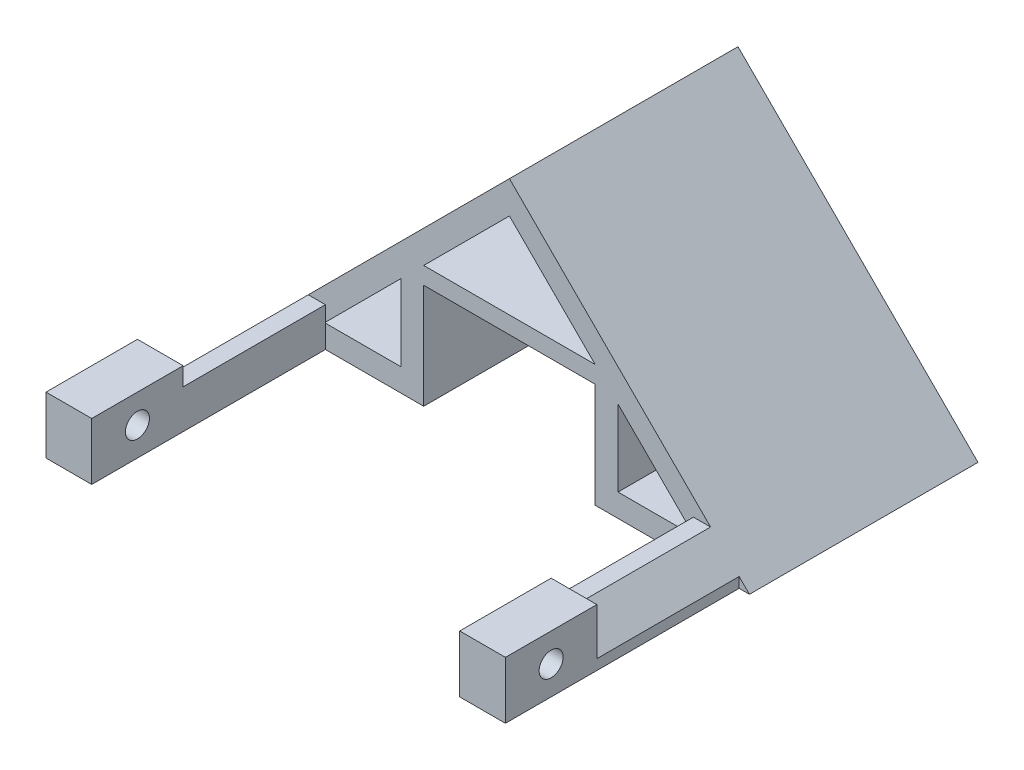
SolidWorks part; units mm, degrees
ref_plane "Front Plane" through (0, 0, 0) normal (0, 0, 1) x (1, 0, 0)
ref_plane "Top Plane" through (0, 0, 0) normal (0, 1, 0) x (1, 0, 0)
ref_plane "Right Plane" through (0, 0, 0) normal (1, 0, 0) x (0, 0, -1)
sketch "Sketch1" plane through (0, 0, 0) normal (0, 0, 1) x (1, 0, 0)
  line L1 (0, 0) -> (-42, -42)
  line L2 (0, -1000.3549) -> (0, 48999.6451) construction
  line L3 (-32.3431, -38) -> (-19, -24.6569)
  line L4 (32.3431, -38) -> (19, -24.6569)
  line L5 (0, 0) -> (42, -42)
  line L7 (-42, -42) -> (-15, -42)
  line L8 (-32.3431, -38) -> (-19, -38)
  line L9 (-34, -34) -> (34, -34) construction
  line L10 (-15, -42) -> (-15, -23.6569)
  line L11 (15, -42) -> (15, -23.6569)
  line L12 (15, -42) -> (42, -42)
  line L13 (19, -38) -> (32.3431, -38)
  line L14 (-19, -38) -> (-19, -24.6569)
  line L15 (19, -38) -> (19, -24.6569)
  line L16 (-15, -20.6569) -> (0, -5.6569)
  line L17 (15, -20.6569) -> (0, -5.6569)
  line L18 (15, -20.6569) -> (-15, -20.6569)
  line L19 (15, -23.6569) -> (-15, -23.6569)
  point P21 (0, -23.6569)
  dimension "D1" = 90
  dimension "D2" = 4
  dimension "D3" = 4
  dimension "D4" = 68
  dimension "D5" = 8
  dimension "D6" = 30
  dimension "D7" = 4
  dimension "D8" = 3
extrude "Boss-Extrude1" add sketch "Sketch1" along normal mid plane 40
sketch "Sketch2" plane through (0, 0, 0) normal (1, 0, 0) x (0, 0, -1)
  line L0 (0, -1034.3624) -> (0, 48965.6376) construction
  line L1 (-20, -42) -> (20, -42) construction
  line L2 (-3.5, -42) -> (-3.5, -65.5)
  line L3 (-3.5, -65.5) -> (-9, -65.5)
  line L4 (-9, -65.5) -> (-9, -69)
  line L5 (-9, -69) -> (9, -69)
  line L6 (9, -65.5) -> (9, -69)
  line L7 (3.5, -65.5) -> (9, -65.5)
  line L8 (3.5, -42) -> (3.5, -65.5)
  line L9 (3.5, -42) -> (-3.5, -42)
  point P5 (0, -42)
  dimension "D1" = 7
  dimension "D2" = 3.5
  dimension "D3" = 27
  dimension "D4" = 18
extrude "Boss-Extrude2" [suppressed] add sketch "Sketch2" along normal blind 6 from vertex starting at point (-42, -42, 0)
sketch "Sketch4" [suppressed] plane through (0, 0, 0) normal (1, 0, 0) x (0, 0, -1)
  line L0 (-20, -38.4859) -> (20, -38.4859) construction
  line L1 (3.5, -38.4859) -> (13.5, -38.4859)
  line L2 (3.5, -38.4859) -> (3.5, -65.4859)
  line L3 (3.5, -65.4859) -> (13.5, -65.4859)
  line L4 (13.5, -38.4859) -> (13.5, -65.4859)
  line L5 (-9, -65.4859) -> (9, -65.4859) construction
  line L7 (-11, -38.4859) -> (-18.5, -38.4859)
  line L8 (-11, -38.4859) -> (-11, -65.4859)
  line L9 (-11, -65.4859) -> (-18.5, -65.4859)
  line L10 (-18.5, -38.4859) -> (-18.5, -65.4859)
  line L11 (-9, -61.9859) -> (-9, -65.4859) construction
  dimension "D1" = 10
  dimension "D2" = 2
  dimension "D3" = 7.5
extrude "Boss-Extrude3" [suppressed] add sketch "Sketch4" against normal blind 6 from vertex starting at point (42, -38.4859, 20)
sketch "Sketch5" plane through (0, 0, 20) normal (0, 0, 1) x (1, 0, 0)
  line L1 (0, 0) -> (-42, -42) construction
  line L2 (-35.2, -35.2) -> (-32.2, -35.2)
  line L3 (-32.2, -35.2) -> (-32.2, -42)
  line L4 (-42, -42) -> (-15, -42) construction
  line L5 (-32.2, -42) -> (-40.2, -42)
  line L6 (-40.2, -42) -> (-40.2, -40.2)
  line L7 (-40.2, -40.2) -> (-35.2, -35.2)
  line L8 (-40.4, 43.0678) -> (-40.4, -67) construction
  dimension "D1" = 8
  dimension "D2" = 3
  dimension "D3" = 0.2
extrude "Boss-Extrude4" add sketch "Sketch5" along normal up to surface (24.9 mm away)
sketch "Sketch6" plane through (0, 0, 44.9) normal (0, 0, 1) x (1, 0, 0)
  line L0 (-40.2, -40.2) -> (-40.2, -42) construction
  line L1 (-32.2, -42) -> (-40.2, -42)
  line L2 (-32.2, -42) -> (-32.2, -32)
  line L3 (-32.2, -32) -> (-40.2, -32)
  line L4 (-40.2, -42) -> (-40.2, -32)
  line L5 (-32.2, -42) -> (-32.2, -35.2) construction
  line L6 (-40.2, -42) -> (-32.2, -42) construction
  dimension "D1" = 10
  dimension "D2" = 0
extrude "Boss-Extrude5" add sketch "Sketch6" along normal blind 16
sketch "Sketch7" plane through (-32.2, 0, 0) normal (1, 0, 0) x (0, 0, -1)
  line L0 (-60.9, -32) -> (-44.9, -32) construction
  line L1 (-60.9, -42) -> (-60.9, -32) construction
  circle A0 centre (-52.9, -37) radius 2.1
  point P5 (-52.9, -32)
  point P8 (-60.9, -37)
  dimension "D1" = 4.2
extrude "Cut-Extrude1" cut sketch "Sketch7" against normal through all
mirror "Mirror1" about plane through (0, 0, 0) normal (1, 0, 0) of "Cut-Extrude1", "Boss-Extrude5", "Boss-Extrude4"
equation "\"width\"= 24"
equation "\"thk\"= 3"
equation "\"holesize\"= 4.2"
equation "\"holedistance\"= ( 20 + 12 ) / 2"
equation "\"threaded_hole\"= 3.9"
equation "\"fillet_radius\"= 2"
equation "\"ground_clearance\"= 25"
equation "\"tire_thk\"= 3"
equation "\"innerwheel_diam\" = \"wheel_diam\"-2*\"tire_thk\""
equation "\"innerwheel_thk\"= 8"
equation "\"wheel_diam\"= 2*(\"width\"/2+\"ground_clearance\")"
equation "\"coloursensor_holesize\"= 2.65"
equation "\"hole_to_edge\" = 4"
equation "\"D1@Sketch7\"=\"holesize\""
equation "\"D7@Sketch1\"=\"D2@Sketch1\""
